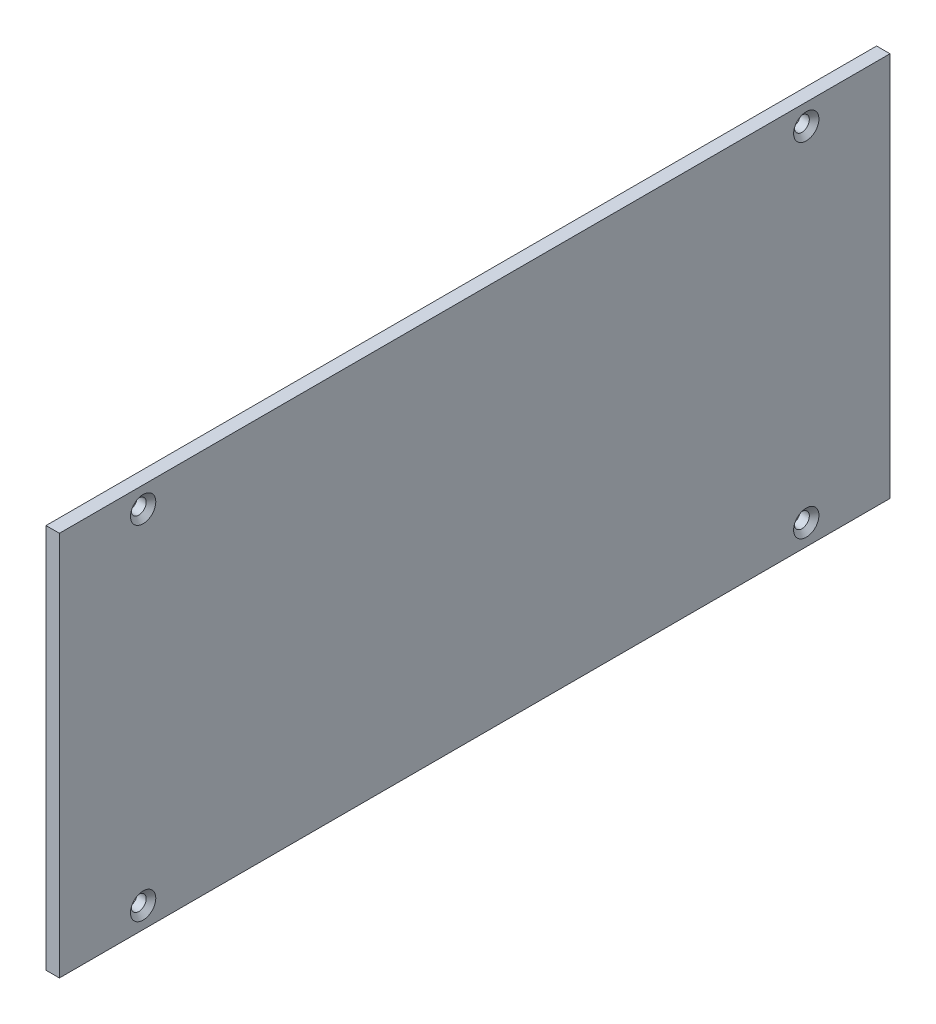
SolidWorks part; units mm, degrees
material "6061-T4 (SS)"
ref_plane "Front Plane" through (0, 0, 0) normal (0, 0, 1) x (1, 0, 0)
ref_plane "Top Plane" through (0, 0, 0) normal (0, 1, 0) x (1, 0, 0)
ref_plane "Right Plane" through (0, 0, 0) normal (1, 0, 0) x (0, 0, -1)
sketch "Sketch1" plane through (0, 0, 0) normal (1, 0, 0) x (0, 0, -1)
  line L1 (0, 0) -> (99.2004, 0)
  line L2 (0, 0) -> (0, 46)
  line L3 (0, 46) -> (99.2004, 46)
  line L4 (99.2004, 0) -> (99.2004, 46)
  dimension "D1" = 46
  dimension "D2" = 99.2004
extrude "Boss-Extrude1" add sketch "Sketch1" along normal blind 1.6002
hole_wizard "CSK for #0 Flat Head Machine Screw (100)1" positions "Sketch3" profile "Sketch4" countersink size "#0" standard "ANSI Inch" end condition through all
sketch "Sketch3" plane through (1.6002, 0, 0) normal (1, 0, 0) x (0, 0, -1)
  line L0 (10, 43.5) -> (10, 2.5) construction
  line L1 (10, 2.5) -> (89.2004, 2.5) construction
  line L2 (89.2004, 2.5) -> (89.2004, 43.5) construction
  line L3 (89.2004, 43.5) -> (10, 43.5) construction
  line L5 (0, 23) -> (10, 23) construction
  line L6 (0, 46) -> (0, 0) construction
  line L7 (10, 23) -> (89.2004, 23) construction
  line L8 (89.2004, 23) -> (99.2004, 23) construction
  line L9 (99.2004, 0) -> (99.2004, 46) construction
  line L11 (99.2004, 46) -> (0, 46) construction
  line L12 (0, 0) -> (99.2004, 0) construction
  point P0 (10, 43.5)
  point P2 (10, 2.5)
  point P4 (89.2004, 2.5)
  point P6 (89.2004, 43.5)
  dimension "D1" = 10
  dimension "D2" = 2.5
  dimension "D3" = 2.5
  dimension "D4" = 10
sketch "Sketch4" plane through (1.6002, 43.5, -10) normal (0, 1, 0) x (0, 0, -1)
  line L0 (0, 0) -> (0, 1.6002)
  line L1 (0, 1.6002) -> (0.889, 1.6002)
  line L2 (0.889, 1.6002) -> (0.889, 0.5222)
  line L3 (0.889, 0.5222) -> (1.5113, 0)
  line L5 (1.5113, 0) -> (0, 0)
  line L6 (-0.889, 0.5222) -> (-1.5113, 0) construction
  line L11 (0, -6.35) -> (0, 107.95) construction
  dimension "Thru Hole Dia." = 1.778
  dimension "Thru Hole Depth" = 1.6002
  dimension "Near C'Sink Dia." = 3.0226
  dimension "Near C'Sink Angle" = 100
